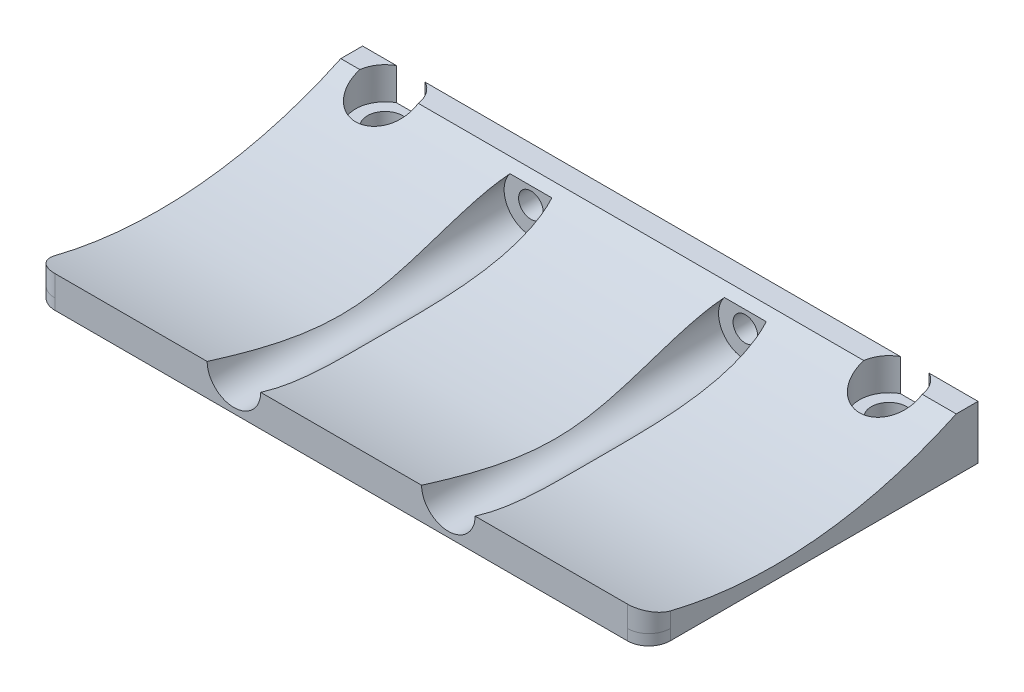
SolidWorks part; units mm, degrees
ref_plane "Front Plane" through (0, 0, 0) normal (0, 0, 1) x (1, 0, 0)
ref_plane "Top Plane" through (0, 0, 0) normal (0, 1, 0) x (1, 0, 0)
ref_plane "Right Plane" through (0, 0, 0) normal (1, 0, 0) x (0, 0, -1)
sketch "Sketch1" plane through (0, 0, 0) normal (0, 1, 0) x (1, 0, 0)
  line L0 (4.5, 28.3) -> (4.5, 4.7) construction
  line L1 (0, 0) -> (57.4, 0)
  line L2 (0, 0) -> (0, 33)
  line L3 (0, 33) -> (57.4, 33)
  line L4 (57.4, 0) -> (57.4, 33)
  circle A0 centre (4.5, 28.3) radius 1.65
  circle A1 centre (51.5, 28.3) radius 1.65
  circle A2 centre (4.5, 4.7) radius 1.65
  circle A3 centre (51.5, 4.7) radius 1.65
  point P13 (0, 16.5)
  point P14 (4.5, 16.5)
  dimension "D3" = 3.3
  dimension "D4" = 47
  dimension "D5" = 23.6
  dimension "D6" = 4.5
  dimension "D1" = 57.4
  dimension "D2" = 33
extrude "Boss-Extrude1" add sketch "Sketch1" along normal blind 1
sketch "Sketch2" plane through (0, 1, 0) normal (0, 1, 0) x (1, 0, 0)
  line L0 (57.4, 0) -> (57.4, 33) construction
  line L1 (0, 33) -> (57.4, 33)
  line L2 (0, 33) -> (0, 30.7)
  line L3 (0, 30.7) -> (57.4, 30.7)
  line L4 (57.4, 33) -> (57.4, 30.7)
  dimension "D1" = 2.3
extrude "Cut-Extrude1" cut sketch "Sketch2" against normal up to next
sketch "Sketch3" plane through (57.4, 0, 0) normal (1, 0, 0) x (0, 0, -1)
  line L0 (30.7, 1) -> (30.7, 5)
  line L1 (30.7, 5) -> (28.7, 5)
  line L2 (28.7, 5) -> (20.7, 1)
  line L3 (0, 1) -> (30.7, 1) construction
  line L4 (20.7, 1) -> (30.7, 1)
  dimension "D1" = 4
  dimension "D2" = 10
  dimension "D3" = 2
extrude "Boss-Extrude2" add sketch "Sketch3" against normal up to surface (57.4 mm away) up to face at (0, 0.5, -15.35)
fillet "Fillet1" radius 2 2 edges at (0, 0.5, 0) (57.4, 0.5, 0)
sketch "Sketch10" plane through (0, 0, 0) normal (1, 0, 0) x (0, 0, -1)
  line L0 (2, 1) -> (0, 1) construction
  line L1 (0, 1) -> (0, 0) construction
  line L2 (0, 0) -> (2, 0) construction
  line L3 (20.7, 1) -> (2, 1) construction
  line L4 (2, 0) -> (30.7, 0) construction
  line L5 (30.7, 0) -> (30.7, 5) construction
  line L6 (30.7, 5) -> (28.7, 5) construction
  line L7 (28.7, 5) -> (20.7, 1) construction
  line L8 (2, 1) -> (0, 1)
  line L9 (0, 1) -> (0, 0)
  line L10 (0, 0) -> (2, 0)
  line L11 (20.7, 1) -> (2, 1)
  line L12 (2, 0) -> (30.7, 0)
  line L13 (30.7, 0) -> (30.7, 5)
  line L14 (30.7, 5) -> (28.7, 5)
  line L15 (28.7, 5) -> (20.7, 1)
  line L16 (0, 1) -> (0, 2.9741)
  line L17 (28.7, 5) -> (28.6687, 5)
  circle A0 centre (11.703, 41.2238) radius 40
  dimension "D1" = 80
extrude "Boss-Extrude3" add sketch "Sketch10" along direction (-1, 0, 0) on the side of the normal up to surface (57.4 mm away) contours A0 L16 L8 L11 L15 L17 region at (0, 1.2898, -1) up to face at (57.4, 2, -19.1333)
sketch "Sketch4" plane through (0, 0, 0) normal (0, -1, 0) x (-1, 0, 0)
  circle A0 centre (-4.5, 28.3) radius 1.65
  circle A1 centre (-51.5, 28.3) radius 1.65
  dimension "D1" = 3.3
extrude "Cut-Extrude2" cut sketch "Sketch4" against normal blind 2
sketch "Sketch5" plane through (0, 2, 0) normal (0, -1, 0) x (-1, 0, 0)
  circle A0 centre (-4.5, 28.3) radius 2.75
  circle A1 centre (-51.5, 28.3) radius 2.75
  dimension "D1" = 5.5
extrude "Cut-Extrude3" cut sketch "Sketch5" against normal up to next
sketch "Sketch6" plane through (0, 0, -30.7) normal (0, 0, -1) x (-1, 0, 0)
  circle A0 centre (-38.7, 3) radius 1.15
  circle A1 centre (-18.7, 3) radius 1.15
  dimension "D1" = 2.3
extrude "Cut-Extrude4" cut sketch "Sketch6" against normal blind 3
sketch "Sketch9" plane through (0, 0, -27.7) normal (0, 0, -1) x (-1, 0, 0)
  circle A0 centre (-38.7, 3) radius 2.5
  circle A1 centre (-18.7, 3) radius 2.5
  dimension "D1" = 5
extrude "Cut-Extrude5" cut sketch "Sketch9" against normal through all
fillet "Fillet2" radius 2 2 edges at (0, 1.9871, 0) (57.4, 1.9871, 0)
